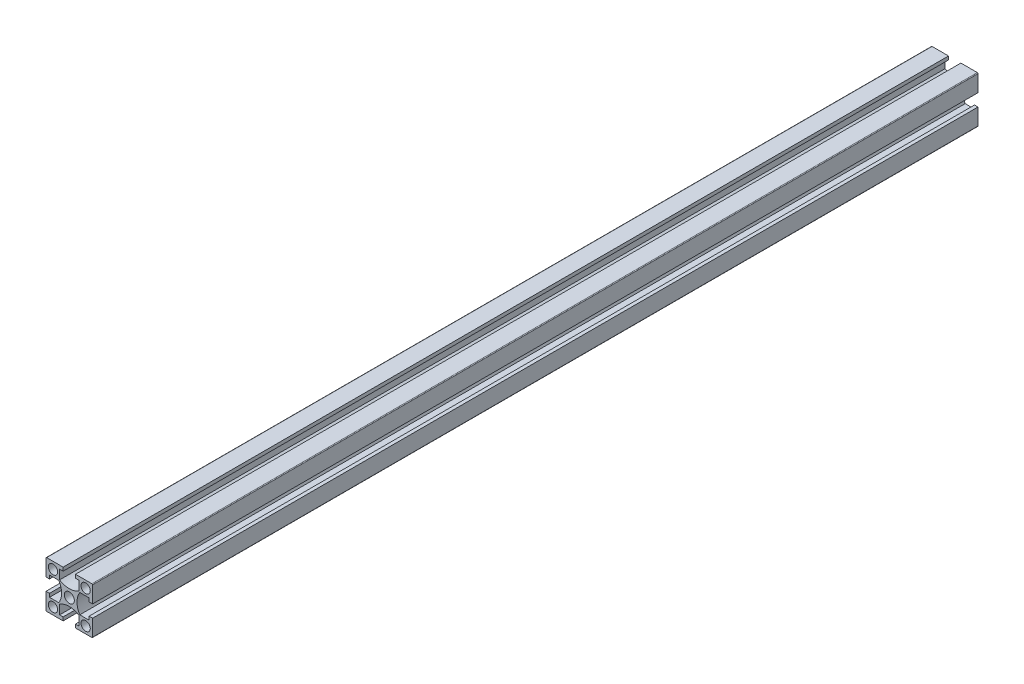
SolidWorks part; units mm, degrees
material "3.0255 (EN-AW 1350A)"
ref_plane "정면" through (0, 0, 0) normal (0, 0, 1) x (1, 0, 0)
ref_plane "윗면" through (0, 0, 0) normal (0, 1, 0) x (1, 0, 0)
ref_plane "우측면" through (0, 0, 0) normal (1, 0, 0) x (0, 0, -1)
sketch "스케치1" plane through (0, 0, 0) normal (0, 0, 1) x (1, 0, 0)
  line L0 (0, 32.0265) -> (0, -31.6588) construction
  line L1 (-10, 10) -> (-10, -10)
  line L2 (-10, 10) -> (10, 10)
  line L3 (-10, 2.65) -> (-8.5, 2.65)
  line L4 (13.6618, 0) -> (-11.6993, 0) construction
  line L5 (-8.5, 2.65) -> (-8.5, 4.15)
  line L6 (-8.5, 4.15) -> (-4.5032, 4.15)
  line L7 (-10, -2.65) -> (-8.5, -2.65)
  line L8 (-8.5, -2.65) -> (-8.5, -4.15)
  line L9 (-8.5, -4.15) -> (-4.5032, -4.15)
  line L10 (-10, -10) -> (10, -10)
  line L11 (10, 10) -> (10, -10)
  circle A0 centre (-7, 7) radius 2
  circle A1 centre (-7, -7) radius 2
  arc A2 (-4.5032, 4.15) -> (-4.5032, -4.15) centre (-11.0587, 0) cw
  circle A3 centre (0, 0) radius 2.15
  circle A4 centre (7, 7) radius 2
  circle A5 centre (7, -7) radius 2
  point P21 (-10, 0)
  point P23 (-3.3, 0)
  point P31 (0, -10)
  point P32 (0, 10)
  dimension "D3" = 4
  dimension "D9" = 6.7
  dimension "D10" = 4.3
  dimension "D11" = 7.7587
  dimension "D1" = 20
  dimension "D2" = 20
  dimension "D4" = 14
  dimension "D5" = 14
  dimension "D6" = 5.3
  dimension "D7" = 8.3
  dimension "D8" = 1.5
extrude "보스-돌출1" add sketch "스케치1" along normal blind 380 contours A0 | A4 | A3 | A5 | A1 | A2 L6 L5 L3 L1 L7 L8 L9 | L2 L11 L10 L1 region at (-6.6069, 0, 0) region at (-7, 7, 0) region at (-7, -7, 0) region at (0, 0, 0) region at (7, 7, 0) region at (7, -7, 0)
extrude "컷-돌출1" cut sketch "스케치1<3>" along normal up to next contours A2 L6 L5 L3 L1 L7 L8 L9 region at (-6.6069, 0, 0)
sketch "스케치1<3>" plane through (0, 0, 0) normal (0, 0, 1) x (1, 0, 0) same geometry as "스케치1"
pattern_circular "원형 패턴1" count 4 over 360 about axis through (0, 0, 380) along (0, 0, -1) of "컷-돌출1" reverse direction yes
fillet "필렛1" radius 0.3 4 edges at (10, -10, 190) (-10, -10, 190) (-10, 10, 190) (10, 10, 190)
sketch "스케치2" plane through (-10, 0, 0) normal (-1, 0, 0) x (0, 0, 1)
  line L0 (380, -4.15) -> (380, 4.15) construction
  line L1 (0, 4.15) -> (0, -4.15) construction
  circle A0 centre (11, 0) radius 2.5
  circle A1 centre (369, 0) radius 2.5
  dimension "D1" = 11
  dimension "D2" = 11
extrude "컷-돌출2" cut sketch "스케치2" against normal through all
